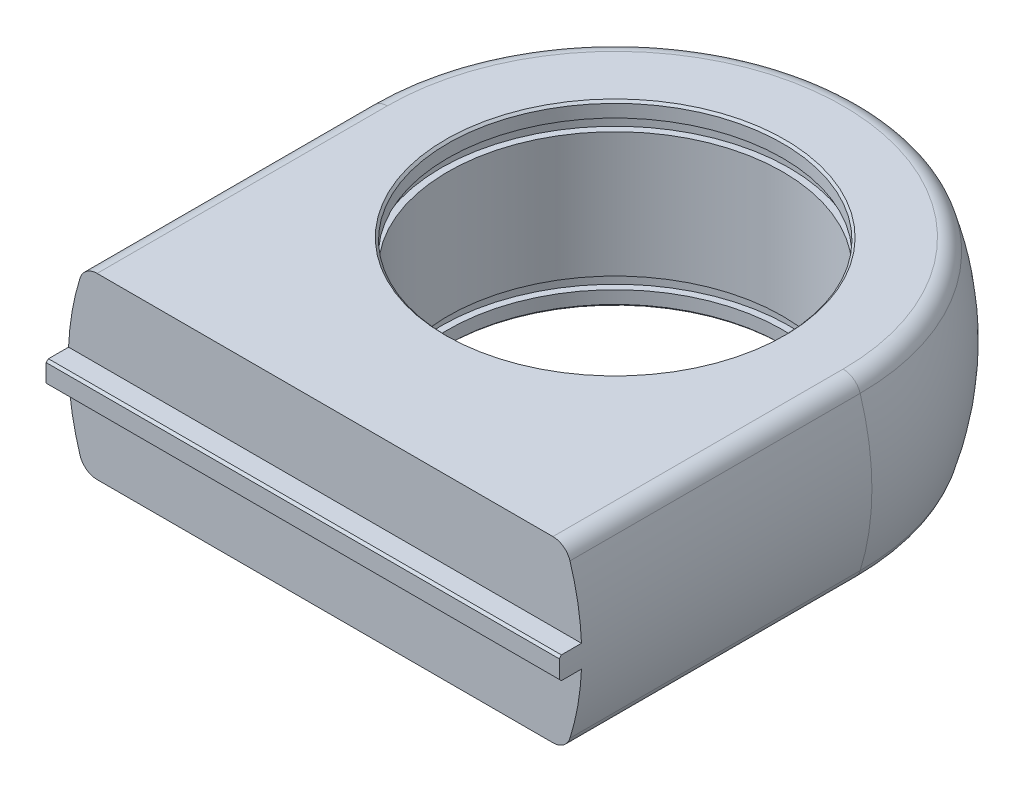
SolidWorks part; units mm, degrees
ref_plane "Front Plane" through (0, 0, 0) normal (0, 0, 1) x (1, 0, 0)
ref_plane "Top Plane" through (0, 0, 0) normal (0, 1, 0) x (1, 0, 0)
ref_plane "Right Plane" through (0, 0, 0) normal (1, 0, 0) x (0, 0, -1)
sketch "Sketch1" plane through (0, 0, 0) normal (0, 1, 0) x (1, 0, 0)
  line L0 (57.5, 65) -> (57.5, 0)
  line L1 (57.5, 0) -> (0, 0)
  line L2 (0, 0) -> (0, 122.5)
  circle A0 centre (0, 65) radius 57.5 construction
  circle A1 centre (0, 65) radius 37.5
  arc A2 (0, 122.5) -> (57.5, 65) centre (0, 65) cw
  dimension "D1" = 115
  dimension "D2" = 75
  dimension "D3" = 65
revolve "Revolve1" add sketch "Sketch1" angle 360 about L2 region at (56.1468, 0, -32.5) region at (15.9155, 0, -65)
sketch "Sketch2" plane through (0, 0, 0) normal (0, 0, 1) x (1, 0, 0)
  line L1 (57.5, 20) -> (-57.5, 20)
  line L2 (57.5, 20) -> (57.5, -20)
  line L3 (57.5, -20) -> (-57.5, -20)
  line L4 (-57.5, 20) -> (-57.5, -20)
  line L5 (57.5, 20) -> (-57.5, -20) construction
  line L6 (57.5, -20) -> (-57.5, 20) construction
  circle A0 centre (0, 0) radius 57.5 construction
  point P0 (0, 0)
  dimension "D1" = 40
extrude "Cut-Extrude1" cut sketch "Sketch2" against normal through all flip side to cut
extrude "Cut-Extrude2" cut sketch "Sketch1<4>" against normal through all both and the other way through all contours A1
sketch "Sketch1<4>" plane through (0, 0, 0) normal (0, 1, 0) x (1, 0, 0) same geometry as "Sketch1"
fillet "Fillet1" radius 4 6 edges at (-53.9096, -20, -32.5) (0, -20, -118.9096) (-53.9096, 20, -32.5) (0, 20, -118.9096) (53.9096, -20, -32.5) (53.9096, 20, -32.5)
sketch "Sketch3" plane through (0, 0, 0) normal (1, 0, 0) x (0, 0, -1)
  line L0 (102.5, 20) -> (27.5, 20) construction
  line L1 (102.5, 14) -> (104, 14)
  line L2 (102.5, 14) -> (102.5, 16.65)
  line L3 (102.5, 16.65) -> (104, 16.65)
  line L4 (104, 14) -> (104, 16.65)
  line L5 (65, -20) -> (65, 20) construction
  line L6 (63.25, 0) -> (-63.25, 0) construction
  line L7 (102.5, -16.65) -> (104, -16.65)
  line L8 (102.5, -14) -> (102.5, -16.65)
  line L9 (102.5, -14) -> (104, -14)
  line L10 (104, -14) -> (104, -16.65)
  dimension "D1" = 1.5
  dimension "D2" = 2.65
  dimension "D3" = 3.35
  dimension "D4" = 37.5
revolve "Cut-Revolve1" cut sketch "Sketch3" angle 360 about axis through (0, -20, -65) along (0, 1, 0)
sketch "Sketch4" plane through (0, 0, 0) normal (0, 0, 1) x (1, 0, 0)
  line L1 (57.5, -2.5) -> (-57.5, -2.5)
  line L2 (57.5, -2.5) -> (57.5, 2.5)
  line L3 (57.5, 2.5) -> (-57.5, 2.5)
  line L4 (-57.5, -2.5) -> (-57.5, 2.5)
  line L5 (57.5, -2.5) -> (-57.5, 2.5) construction
  line L6 (57.5, 2.5) -> (-57.5, -2.5) construction
  arc A0 (-54.8684, 17.1963) -> (-54.8684, -17.1963) centre (0, 0) ccw construction
  point P0 (0, 0)
  arc M5 (-54.8684, 17.1963) -> (-54.8684, -17.1963) centre (0, 0) ccw
  arc M9 (54.8684, -17.1963) -> (54.8684, 17.1963) centre (0, 0) ccw
  dimension "D1" = 5
extrude "Boss-Extrude1" add sketch "Sketch4" along normal blind 5 contours L3 L1 M9 M5 region at (0, 0, 0)
chamfer "Chamfer1" distance 0.5 angle 45 4 edges at (0, -2.5, 5) (0, 2.5, 5) (0, -20, -27.5) (0, 20, -27.5)
